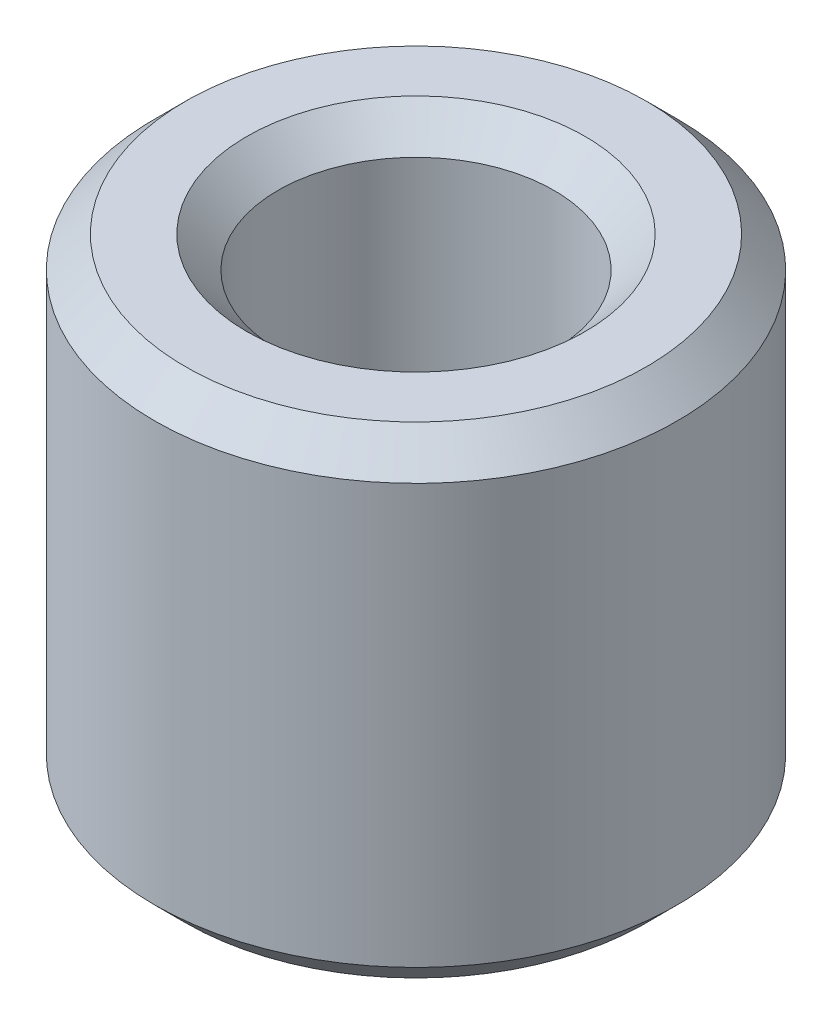
SolidWorks part; units mm, degrees
ref_plane "Front Plane" through (0, 0, 0) normal (0, 0, 1) x (1, 0, 0)
ref_plane "Top Plane" through (0, 0, 0) normal (0, 1, 0) x (1, 0, 0)
ref_plane "Right Plane" through (0, 0, 0) normal (1, 0, 0) x (0, 0, -1)
sketch "Sketch1" plane through (0, 0, 0) normal (0, 1, 0) x (1, 0, 0)
  circle A0 centre (0, 0) radius 7.5
  dimension "SLEEVE_OD" = 15
extrude "Boss-Extrude1" add sketch "Sketch1" along normal blind 13.815
sketch "Sketch2" plane through (0, 0, 0) normal (0, 1, 0) x (1, 0, 0)
  circle A0 centre (0, 0) radius 3.9592
  dimension "BORE_D" = 7.9184
extrude "Cut-Extrude1" cut sketch "Sketch2" along normal through all
chamfer "Chamfer1" distance 0.8937 angle 45 4 edges at (0, 13.815, 3.9592) (0, 0, 3.9592) (0, 0, 7.5) (0, 13.815, 7.5)
